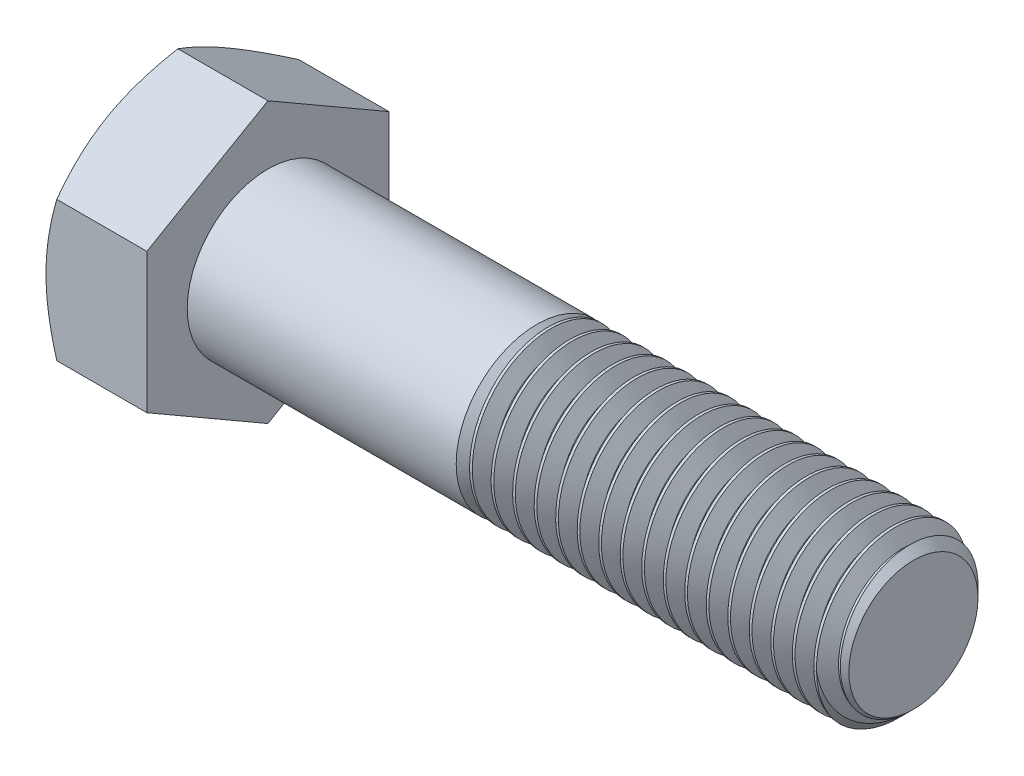
SolidWorks part; units mm, degrees
ref_plane "Front Plane" through (0, 0, 0) normal (0, 0, 1) x (1, 0, 0)
ref_plane "Top Plane" through (0, 0, 0) normal (0, 1, 0) x (1, 0, 0)
ref_plane "Right Plane" through (0, 0, 0) normal (1, 0, 0) x (0, 0, -1)
sketch "Sketch1" plane through (0, 0, 0) normal (0, 0, 1) x (1, 0, 0)
  line L0 (-44.0531, 0) -> (44.0531, 0) construction
  line L1 (44.0531, 9.525) -> (44.0531, -9.525) construction
  line L2 (-32.1469, 14.2875) -> (-32.1469, -14.2875) construction
  line L3 (-44.0531, 14.2875) -> (-44.0531, -14.2875) construction
  point P9 (-32.1469, 0)
  point P10 (35.1631, -9.525)
  dimension "Screw Dia" = 19.05
  dimension "Hex" = 28.575
  dimension "Head Ht" = 11.9062
  dimension "Screw Lenght" = 76.2
  dimension "D1" = 8.89
ref_plane "Plane2" through (44.0531, 0, 0) normal (1, 0, 0) x (0, 0, -1)
sketch "Sketch5" plane through (44.0531, 0, 0) normal (1, 0, 0) x (0, 0, -1)
  circle A0 centre (0, 0) radius 9.525
extrude "Boss-Extrude3" add sketch "Sketch5" against normal up to vertex (76.2 mm away) up to point (-32.1469, 0, 0)
sketch "Sketch9" plane through (44.0531, 0, 0) normal (1, 0, 0) x (0, 0, -1)
  circle A1 centre (0, 0) radius 9.525
  circle A2 centre (0, 0) radius 9.525
  dimension "D1" = 0
curve "Helix/Spiral1" pitch 2.54 height 46.99 turns 18.5 parameters "Pitch"=2.54
chamfer "Chamfer1" distance 1.905 angle 45 1 edges at (44.0531, 0, -9.525)
sketch "Sketch10" plane through (0, 0, 0) normal (0, 0, 1) x (1, 0, 0)
  line L0 (44.0531, 9.525) -> (45.0056, 7.8752)
  line L1 (45.0056, 7.8752) -> (45.3231, 7.8752)
  line L2 (45.3231, 7.8752) -> (46.2756, 9.525)
  line L3 (44.0531, 9.525) -> (46.2756, 9.525)
  line L4 (45.1644, 9.525) -> (45.1644, 7.8752) construction
  line L5 (44.5294, 8.7001) -> (45.7994, 8.7001) construction
  dimension "D1" = 60
  dimension "D2" = 0.3175
  dimension "D3" = 1.27
sweep "Cut-Sweep1" cut profiles "Sketch10" path "Helix/Spiral1" align with end faces yes
sketch "Sketch11" plane through (0, 0, 0) normal (0, 0, 1) x (1, 0, 0)
  line L0 (-32.1469, 9.525) -> (-32.1469, 0)
  line L1 (-32.1469, 0) -> (9.1281, 0)
  line L3 (9.1281, 0) -> (-0.3969, 9.525)
  line L4 (-32.1469, 9.525) -> (-0.3969, 9.525)
  dimension "D1" = 45
  dimension "MIn Thread" = 44.45
revolve "Revolve1" add sketch "Sketch11" angle 360 about L1
sketch "Sketch6" plane through (-32.1469, 0, 0) normal (-1, 0, 0) x (0, 0, 1)
  line L0 (0, 14.2875) -> (0, -14.2875) construction
  line L1 (14.2875, 8.2489) -> (0, 16.4978)
  line L2 (0, 16.4978) -> (-14.2875, 8.2489)
  line L3 (-14.2875, 8.2489) -> (-14.2875, -8.2489)
  line L4 (-14.2875, -8.2489) -> (0, -16.4978)
  line L5 (0, -16.4978) -> (14.2875, -8.2489)
  line L6 (14.2875, -8.2489) -> (14.2875, 8.2489)
  circle A0 centre (0, 0) radius 14.2875 construction
extrude "Boss-Extrude4" add sketch "Sketch6" along normal up to vertex (11.9062 mm away) up to point (-44.0531, -14.2875, 0)
sketch "Sketch7" plane through (-44.0531, 0, 0) normal (-1, 0, 0) x (0, 0, 1)
  circle A0 centre (0, 0) radius 14.2875 construction
  circle A1 centre (0, 0) radius 14.2875
sketch "Sketch8" plane through (-44.0531, 0, 0) normal (-1, 0, 0) x (0, 0, 1)
  circle A0 centre (0, 0) radius 14.2875 construction
  circle A1 centre (0, 0) radius 14.2875
extrude "Cut-Extrude3" cut sketch "Sketch8" against normal through all draft 60 flip side to cut
equation "\"D2@Sketch10\" = \"Pitch@Helix/Spiral1\"*.125"
equation "\"D3@Sketch10\" = \"Pitch@Helix/Spiral1\"*.5"
equation "\"D3@Helix/Spiral1\" = \"MIn Thread@Sketch11\"+\"Pitch@Helix/Spiral1\""
equation "\"D1@Chamfer1\" = \"Pitch@Helix/Spiral1\"*.75"
equation "\"D1@Sketch1\" = \"Pitch@Helix/Spiral1\"*3.5"
